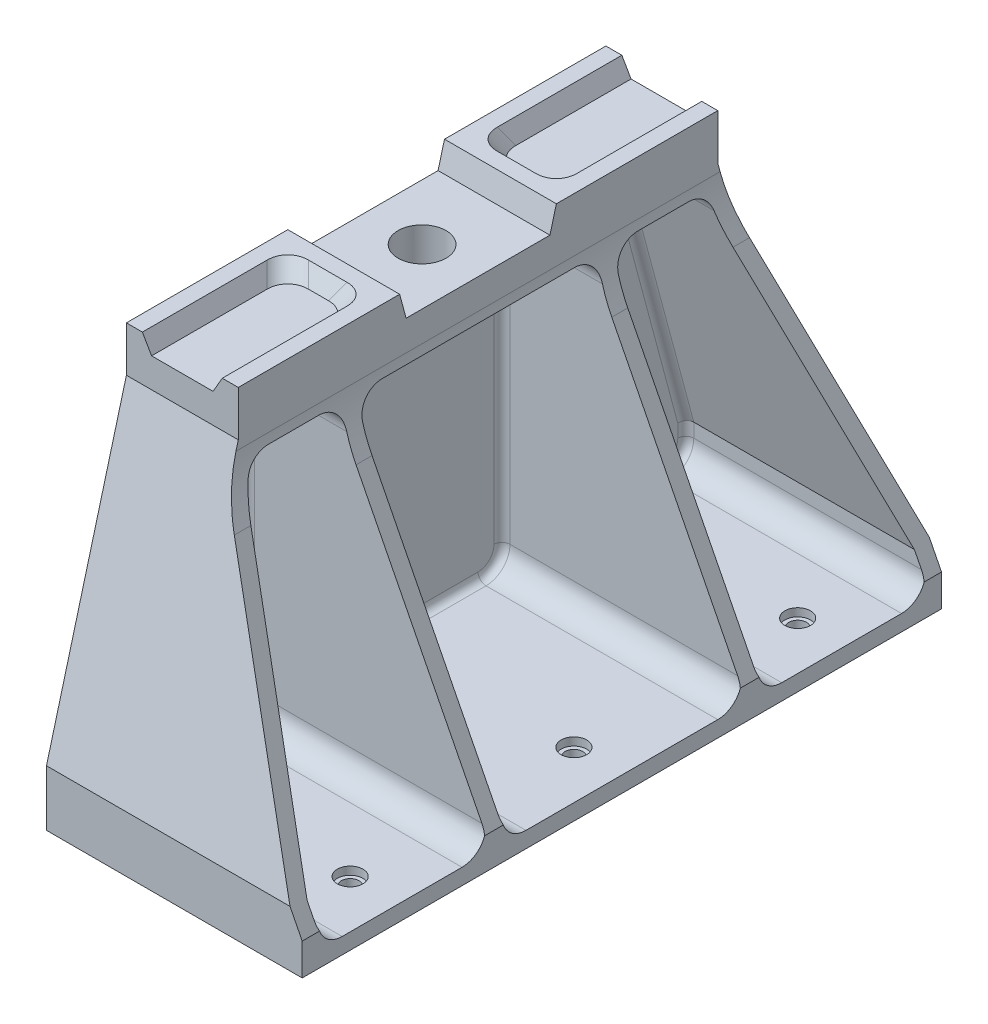
SolidWorks part; units mm, degrees
note: The reader was unsure of these and kept them because the rebuilt part matched: shared geometry of "Sketch2<5>", "Sketch12<3>".
ref_plane "Front Plane" through (0, 0, 0) normal (0, 0, 1) x (1, 0, 0)
ref_plane "Top Plane" through (0, 0, 0) normal (0, 1, 0) x (1, 0, 0)
ref_plane "Right Plane" through (0, 0, 0) normal (1, 0, 0) x (0, 0, -1)
sketch "Sketch1" plane through (0, 0, 0) normal (0, 0, 1) x (1, 0, 0)
  line L0 (0, 0) -> (0, 250)
  line L1 (0, 250) -> (70, 250)
  line L2 (70, 250) -> (70, 197)
  line L3 (70, 197) -> (160, 20)
  line L4 (160, 20) -> (160, 0)
  line L5 (160, 0) -> (0, 0)
  dimension "D1" = 250
  dimension "D2" = 160
  dimension "D3" = 20
  dimension "D4" = 53
  dimension "D5" = 70
extrude "Boss-Extrude1" add sketch "Sketch1" along normal blind 200
sketch "Sketch2" plane through (0, 0, 0) normal (1, 0, 0) x (0, 0, -1)
  line L0 (-150.0007, 250) -> (-150.0007, 221.6)
  line L1 (-150.0007, 221.6) -> (-200, 35)
  line L2 (-200, 0) -> (0, 0) construction
  line L3 (-200, 0) -> (-200, 20) construction
  line L4 (-200, 197) -> (-200, 250) construction
  line L5 (-200, 20) -> (-200, 197) construction
  line L6 (-200, 250) -> (0, 250) construction
  line L7 (-200, 0) -> (0, 0)
  line L8 (-200, 0) -> (-200, 20)
  line L9 (-200, 197) -> (-200, 250)
  line L10 (-200, 20) -> (-200, 197)
  line L11 (-200, 250) -> (0, 250)
  line L12 (0, 250) -> (0, 0) construction
  line L13 (0, 250) -> (0, 0)
  line L14 (-142.7561, 210) -> (-190, 33.6835)
  line L15 (-190, 33.6835) -> (-190, 10)
  line L16 (-190, 10) -> (-85, 10)
  line L17 (-85, 10) -> (-85, 210)
  line L18 (-85, 210) -> (-142.7561, 210)
  line L19 (0, 210) -> (-75, 210)
  line L20 (-75, 210) -> (-75, 10)
  line L21 (-75, 10) -> (0, 10)
  dimension "D1" = 28.4
  dimension "D2" = 15
  dimension "D3" = 35
  dimension "D4" = 10
  dimension "D5" = 10
  dimension "D6" = 105
  dimension "D7" = 200
  dimension "D8" = 10
  dimension "D9" = 10
extrude "Cut-Extrude3" cut sketch "Sketch2" against normal through all both and the other way through all contours L11 L9 L10 L1 L0
extrude "Cut-Extrude4" cut sketch "Sketch2<5>" along normal up to next from offset 10 contours L20 L21 L13 L19 | L17 L18 L14 L15 L16
sketch "Sketch2<5>" plane through (0, 0, 0) normal (1, 0, 0) x (0, 0, -1) same geometry as "Sketch2"
sketch "Sketch4" plane through (0, 250, 0) normal (0, 1, 0) x (1, 0, 0)
  line L0 (0, 0) -> (70, 0) construction
  line L1 (160, 0) -> (10, 0) construction
  line L2 (70, -150.0007) -> (70, 0) construction
  circle A0 centre (35, 0) radius 15
  dimension "D1" = 30
extrude "Cut-Extrude5" cut sketch "Sketch4" against normal up to surface (40 mm away) up to face at (40, 210, 37.5)
sketch "Sketch5" plane through (70, 0, 0) normal (1, 0, 0) x (0, 0, -1)
  line L0 (0, 235) -> (-45, 235)
  line L1 (-45, 235) -> (-49.0192, 250)
  line L11 (-75, 197) -> (-75, 210)
  line L12 (-75, 210) -> (0, 210)
  line L13 (0, 210) -> (0, 250)
  line L14 (0, 250) -> (-150.0007, 250)
  line L15 (-150.0007, 250) -> (-150.0007, 221.6)
  line L16 (-150.0007, 221.6) -> (-156.5922, 197)
  line L17 (-156.5922, 197) -> (-146.2395, 197)
  line L18 (-146.2395, 197) -> (-142.7561, 210)
  line L19 (-142.7561, 210) -> (-85, 210)
  line L20 (-85, 210) -> (-85, 197)
  line L21 (-85, 197) -> (-75, 197)
  line L22 (-75, 197) -> (-75, 210)
  line L23 (-75, 210) -> (0, 210)
  line L24 (0, 210) -> (0, 250)
  line L25 (0, 250) -> (-150.0007, 250)
  line L26 (-150.0007, 250) -> (-150.0007, 221.6)
  line L27 (-150.0007, 221.6) -> (-156.5922, 197)
  line L28 (-156.5922, 197) -> (-146.2395, 197)
  line L29 (-146.2395, 197) -> (-142.7561, 210)
  line L30 (-142.7561, 210) -> (-85, 210)
  line L31 (-85, 210) -> (-85, 197)
  line L32 (-85, 197) -> (-75, 197)
  point P6 (0, 0)
  point P10 (-59.5654, 260.228)
  line M16 (0, 210) -> (0, 250)
  line M17 (0, 250) -> (-150.0007, 250)
  dimension "D2" = 15
  dimension "D3" = 15
  dimension "D4" = 45
  dimension "D1" = 0
extrude "Cut-Extrude6" cut sketch "Sketch5" against normal up to next contours L1 L0 M16 M17
sketch "Sketch6" plane through (0, 250, 0) normal (0, 1, 0) x (1, 0, 0)
  line L0 (35, 0) -> (35, -150.0007) construction
  line L1 (0, -150.0007) -> (70, -150.0007) construction
  line L2 (10, -150.0007) -> (10, -59.0192)
  line L3 (10, -59.0192) -> (60, -59.0192)
  line L4 (70, -49.0192) -> (0, -49.0192)
  line L5 (0, -49.0192) -> (0, -150.0007)
  line L6 (0, -150.0007) -> (70, -150.0007)
  line L7 (70, -150.0007) -> (70, -49.0192)
  line L8 (70, -49.0192) -> (0, -49.0192)
  line L9 (0, -49.0192) -> (0, -150.0007)
  line L10 (0, -150.0007) -> (70, -150.0007)
  line L11 (70, -150.0007) -> (70, -49.0192)
  line L12 (60, -59.0192) -> (60, -150.0007)
  line M7 (0, -150.0007) -> (70, -150.0007)
  dimension "D2" = 50
  dimension "D3" = 10
  dimension "D4" = 10
  dimension "D1" = 0
extrude "Cut-Extrude7" cut sketch "Sketch6" against normal blind 10 contours L0 L3 L2 M7 | L3 L0 L10 L12
chamfer "Chamfer2" distance 10 angle 30 2 edges at (60, 240, 104.51) (10, 240, 104.51)
chamfer "Chamfer3" distance 10 angle 30 1 edges at (35, 240, 59.0192)
fillet "Fillet1" radius 15 8 edges at (57.1132, 245, 61.906) (12.8868, 245, 61.906) (40, 210, 75) (85, 10, 75) (85, 10, 85) (85, 10, 190) (40, 210, 85) (40, 210, 142.7561)
fillet "Fillet4" radius 80 1 edges at (70, 197, 80)
sketch "Sketch12" plane through (0, 10, 0) normal (0, 1, 0) x (1, 0, 0)
  line L0 (30, 0) -> (130, 0) construction
  line L1 (160, 0) -> (10, 0) construction
  line L3 (0, -200) -> (0, 0) construction
  line L4 (0, -200) -> (160, -200) construction
  line L5 (30, -140) -> (130, -140) construction
  line L6 (160, -100) -> (10, -100) construction
  circle A0 centre (130, 0) radius 8
  circle A1 centre (30, 0) radius 8
  circle A2 centre (130, 0) radius 5.5
  circle A3 centre (30, 0) radius 5.5
  circle A4 centre (30, -140) radius 8
  circle A5 centre (30, -140) radius 5.5
  circle A6 centre (130, -140) radius 8
  circle A7 centre (130, -140) radius 5.5
  point P20 (139.044, -140)
  point P21 (0, 0)
  line M4 (160, 0) -> (10, 0)
  dimension "D2" = 16
  dimension "D3" = 11
  dimension "D1" = 100
  dimension "D4" = 30
  dimension "D5" = 200
  dimension "D6" = 140
  dimension "D7" = 100
extrude "Cut-Extrude9" cut sketch "Sketch12" against normal blind 10 contours A3 M4 | A2 M4 | A7 | A5
extrude "Cut-Extrude10" cut sketch "Sketch12<3>" against normal blind 5 contours A2 A0 M4 | A3 A1 M4 | A6 A7 | A4 A5
sketch "Sketch12<3>" plane through (0, 10, 0) normal (0, 1, 0) x (1, 0, 0) same geometry as "Sketch12"
fillet "Fillet5" radius 5 14 edges at (10, 10, 30) (10, 14.3934, 70.6066) (10, 110, 75) (10, 205.6066, 70.6066) (10, 14.3934, 185.6066) (10, 29.3417, 190) (10, 116.2829, 167.8676) (10, 206.9003, 140.3776) (10, 210, 115.6231) (10, 205.6066, 89.3934) (10, 110, 85) (10, 14.3934, 89.3934) (10, 10, 137.5) (10, 210, 30)
mirror "Mirror1" about plane through (0, 0, 0) normal (0, 0, -1) of bodies 110
